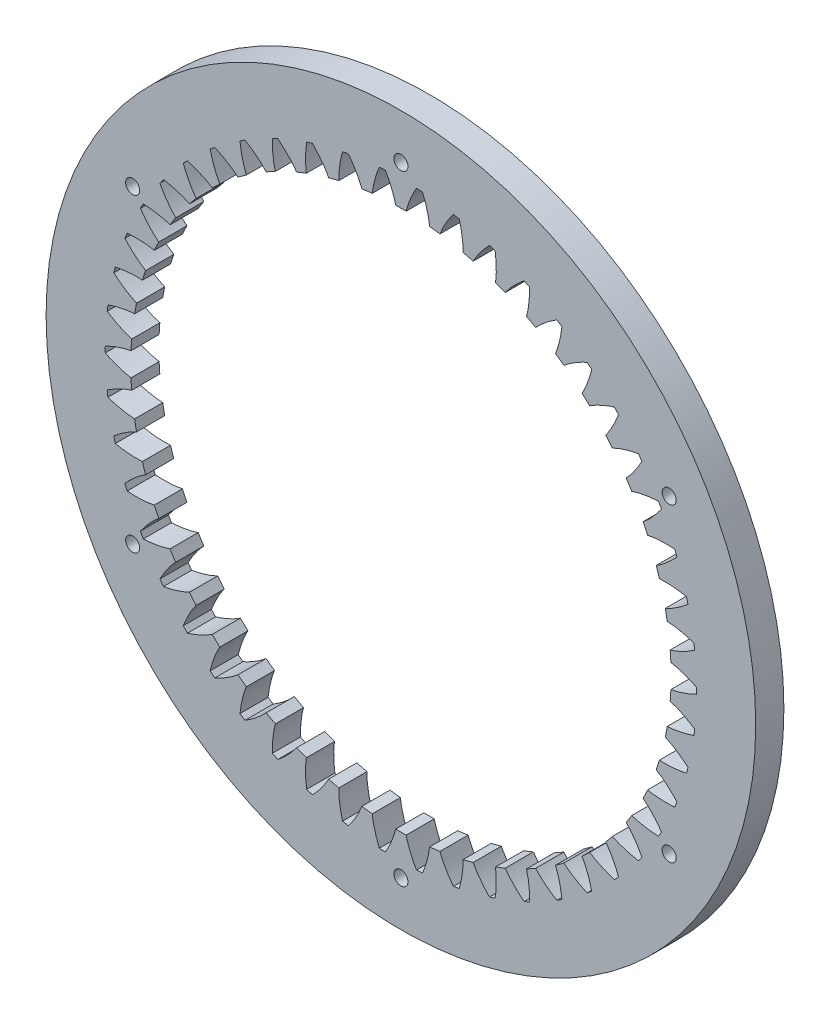
SolidWorks part; units mm, degrees
ref_plane "前视基准面" through (0, 0, 0) normal (0, 0, 1) x (1, 0, 0)
ref_plane "上视基准面" through (0, 0, 0) normal (0, 1, 0) x (1, 0, 0)
ref_plane "右视基准面" through (0, 0, 0) normal (1, 0, 0) x (0, 0, -1)
sketch "草图1" plane through (0, 0, 0) normal (0, 0, 1) x (1, 0, 0)
  circle A0 centre (0, 0) radius 52.5
  circle A1 centre (0, 0) radius 57
extrude "凸台-拉伸1" add sketch "草图1" along normal blind 5
ref_axis "基准轴1" through (0, 0, -0.25) along (0, 0, 1)
sketch "草图2" plane through (0, 0, 0) normal (0, 0, 1) x (1, 0, 0)
  line L0 (0, 0) -> (0, 48) construction
  arc A0 (0.9285, 47.9627) -> (-0.9285, 47.9627) centre (0, 0) ccw
  arc A1 (3.0929, 52.9989) -> (-3.0929, 52.9989) centre (0, 0) ccw
  arc A2 (-3.0929, 52.9989) -> (3.0929, 52.9989) centre (0, 0) ccw construction
  spline S0 degree 3 poles (0.9285, 47.9627) (0.9597, 48.1008) (1.0134, 48.3161) (1.0965, 48.613) (1.1714, 48.8613) (1.257, 49.126) (1.3541, 49.4067) (1.4632, 49.7031) (1.5851, 50.0147) (1.7204, 50.3412) (1.8697, 50.6821) (2.0337, 51.037) (2.2129, 51.4055) (2.4081, 51.787) (2.6962, 52.3236) (2.9292, 52.7274) (3.0929, 52.9989) knots 0 0 0 0 0.077192 0.120911 0.168044 0.218592 0.272555 0.329933 0.390726 0.454933 0.522555 0.593592 0.668044 0.745911 0.827192 1 1 1 1
  spline S1 degree 3 poles (-0.9285, 47.9627) (-0.9597, 48.1008) (-1.0134, 48.3161) (-1.0965, 48.613) (-1.1714, 48.8613) (-1.257, 49.126) (-1.3541, 49.4067) (-1.4632, 49.7031) (-1.5851, 50.0147) (-1.7204, 50.3412) (-1.8697, 50.6821) (-2.0337, 51.037) (-2.2129, 51.4055) (-2.4081, 51.787) (-2.6962, 52.3236) (-2.9292, 52.7274) (-3.0929, 52.9989) knots 0 0 0 0 0.077192 0.120911 0.168044 0.218592 0.272555 0.329933 0.390726 0.454933 0.522555 0.593592 0.668044 0.745911 0.827192 1 1 1 1
extrude "凸台-拉伸2" add sketch "草图2" along normal blind 5
pattern_circular "阵列(圆周)1" count 50 every 7.2 about axis through (0, 0, -0.25) along (0, 0, 1) of "凸台-拉伸2"
sketch "草图3" plane through (0, 0, 0) normal (0, 0, 1) x (1, 0, 0)
  circle A0 centre (0, 0) radius 50 construction
  dimension "Dn" = 100
sketch "草图4" plane through (0, 0, 5) normal (0, 0, 1) x (1, 0, 0)
  circle A0 centre (0, 0) radius 63
  circle A1 centre (0, 0) radius 57
  circle A2 centre (0, 0) radius 57 construction
  dimension "D1" = 126
extrude "凸台-拉伸3" add sketch "草图4" against normal blind 5
sketch "草图5" plane through (0, 0, 5) normal (0, 0, 1) x (1, 0, 0)
  line L1 (0, 55) -> (-47.6314, 27.5) construction
  line L2 (-47.6314, 27.5) -> (-47.6314, -27.5) construction
  line L3 (-47.6314, -27.5) -> (0, -55) construction
  line L4 (0, -55) -> (47.6314, -27.5) construction
  line L5 (47.6314, -27.5) -> (47.6314, 27.5) construction
  line L6 (47.6314, 27.5) -> (0, 55) construction
  circle A0 centre (0, 0) radius 55 construction
  circle A1 centre (0, 0) radius 47.6314 construction
  circle A2 centre (0, 55) radius 1.25
  circle A3 centre (47.6314, 27.5) radius 1.25
  circle A4 centre (47.6314, -27.5) radius 1.25
  circle A5 centre (0, -55) radius 1.25
  circle A6 centre (-47.6314, -27.5) radius 1.25
  circle A7 centre (-47.6314, 27.5) radius 1.25
  point P3 (0, 0)
  point P24 (0, 0)
  dimension "D1" = 110
  dimension "D2" = 2.5
  dimension "D3" = 6
extrude "切除-拉伸1" cut sketch "草图5" against normal up to next
